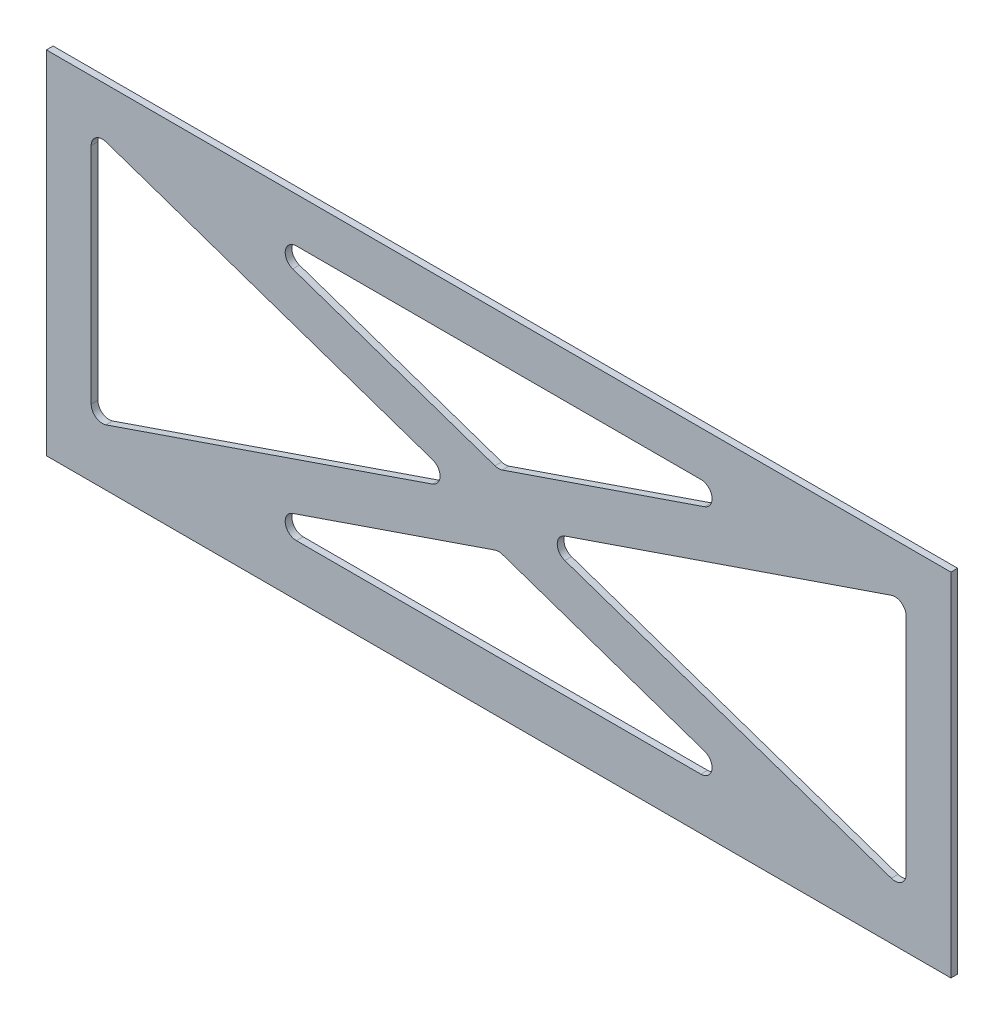
SolidWorks part; units mm, degrees
ref_plane "Front Plane" through (0, 0, 0) normal (0, 0, 1) x (1, 0, 0)
ref_plane "Top Plane" through (0, 0, 0) normal (0, 1, 0) x (1, 0, 0)
ref_plane "Right Plane" through (0, 0, 0) normal (1, 0, 0) x (0, 0, -1)
sketch "Sketch1" plane through (0, 0, 152) normal (0, 0, 1) x (1, 0, 0)
  line L1 (-67.5, 68) -> (336.5, 68)
  line L2 (-67.5, 68) -> (-67.5, -89)
  line L3 (-67.5, -89) -> (336.5, -89)
  line L4 (336.5, 68) -> (336.5, -89)
  line L6 (-47.5, -59.0001) -> (-47.5, 41.0001)
  line L7 (-40.8784, 45.7298) -> (104.9597, -4.2703)
  line L8 (234.5, 66) -> (-65.5, 66) construction
  line L9 (-65.5, -84) -> (-65.5, 66) construction
  line L10 (234.5, -84) -> (-65.5, -84) construction
  line L12 (334.5, -84) -> (-65.5, -84) construction
  line L13 (334.5, 66) -> (334.5, -84) construction
  line L14 (-65.5, -84) -> (-65.5, 66) construction
  line L15 (-65.5, 66) -> (334.5, 66) construction
  line L18 (224.8307, 48) -> (44.1693, 48)
  line L19 (104.9597, -13.7297) -> (-40.8784, -63.7298)
  line L20 (42.5477, 38.2703) -> (132.8784, 7.3007)
  line L21 (136.1216, 7.3007) -> (226.4523, 38.2703)
  line L22 (334.5, -49) -> (334.5, 31) construction
  line L23 (309.8784, 45.7298) -> (164.0403, -4.2703)
  line L24 (316.5, -59.0001) -> (316.5, 41.0001)
  line L25 (164.0403, -13.7297) -> (309.8784, -63.7298)
  line L26 (-65.5, -9) -> (334.5, -9) construction
  line L27 (42.5477, -56.2703) -> (132.8784, -25.3007)
  line L28 (224.8307, -66) -> (44.1693, -66)
  line L29 (136.1216, -25.3007) -> (226.4523, -56.2703)
  line L30 (134.5, 6.7448) -> (134.5, -24.7448) construction
  line L31 (118.7552, -9) -> (150.2448, -9) construction
  line L32 (134.5, 6.7448) -> (134.5, -24.7448) construction
  arc A0 (-40.8784, -63.7298) -> (-47.5, -59.0001) centre (-42.5, -59.0001) cw
  arc A1 (104.9597, -13.7297) -> (104.9597, -4.2703) centre (103.3381, -9) ccw
  arc A2 (-40.8784, 45.7298) -> (-47.5, 41.0001) centre (-42.5, 41.0001) ccw
  arc A3 (226.4523, -56.2703) -> (224.8307, -66) centre (224.8307, -61) cw
  arc A4 (42.5477, -56.2703) -> (44.1693, -66) centre (44.1693, -61) ccw
  arc A5 (132.8784, -25.3007) -> (136.1216, -25.3007) centre (134.5, -30.0305) cw
  arc A6 (164.0403, -4.2703) -> (164.0403, -13.7297) centre (165.6619, -9) ccw
  arc A7 (309.8784, -63.7298) -> (316.5, -59.0001) centre (311.5, -59.0001) ccw
  arc A8 (316.5, 41.0001) -> (309.8784, 45.7298) centre (311.5, 41.0001) ccw
  arc A9 (42.5477, 38.2703) -> (44.1693, 48) centre (44.1693, 43) cw
  arc A10 (226.4523, 38.2703) -> (224.8307, 48) centre (224.8307, 43) ccw
  arc A11 (136.1216, 7.3007) -> (132.8784, 7.3007) centre (134.5, 12.0305) cw
  point P14 (134.5, -9)
  point P15 (134.5, -9)
  point P32 (-47.5, 48)
  point P35 (254.8316, -66)
  point P38 (14.1684, -66)
  point P51 (14.1684, 48)
  point P54 (254.8316, 48)
  point P65 (-67.5, 68)
  point P66 (-67.5, 68)
  dimension "D9" = 5
  dimension "D10" = 5
  dimension "D1" = 2
  dimension "D2" = 2
  dimension "D3" = 2
  dimension "D4" = 5
  dimension "D5" = 20
  dimension "D6" = 20
  dimension "D7" = 20
  dimension "D8" = 20
  dimension "D11" = 20
extrude "Boss-Extrude1" add sketch "Sketch1" along normal blind 3
